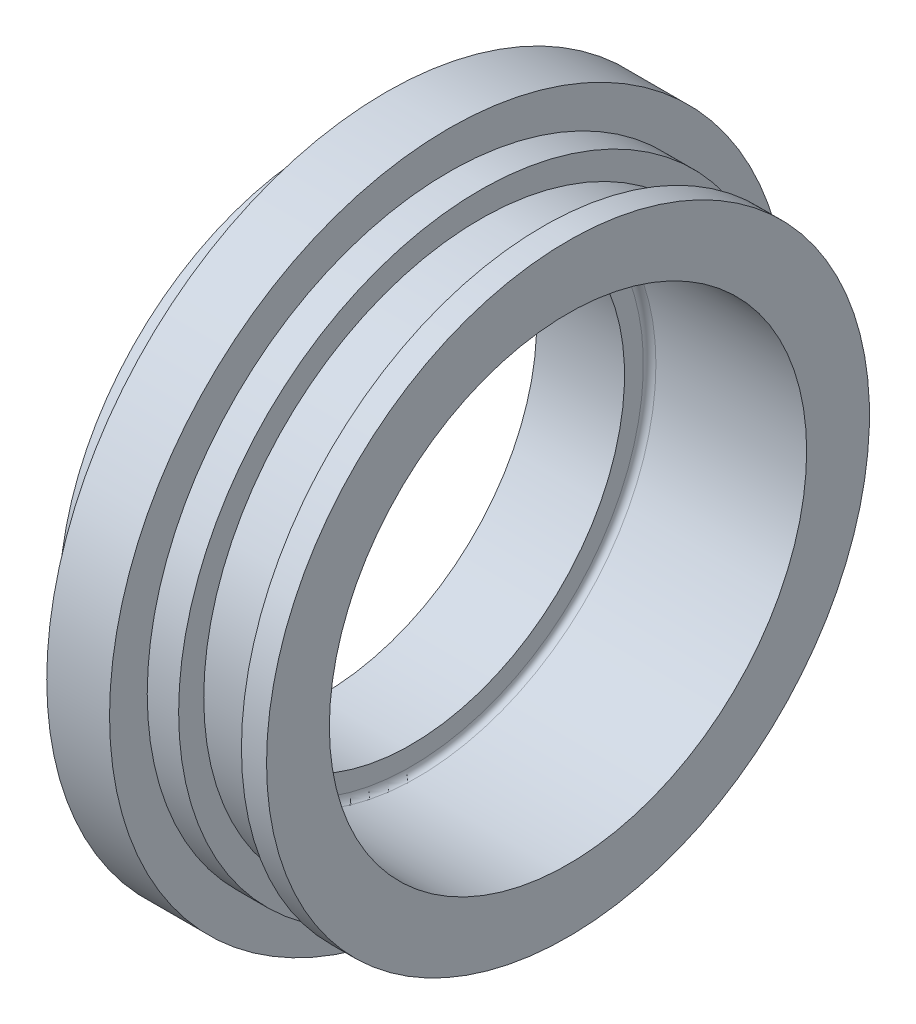
SolidWorks part; units mm, degrees
ref_plane "Přední rovina" through (0, 0, 0) normal (0, 0, 1) x (1, 0, 0)
ref_plane "Horní rovina" through (0, 0, 0) normal (0, 1, 0) x (1, 0, 0)
ref_plane "Pravá rovina" through (0, 0, 0) normal (1, 0, 0) x (0, 0, -1)
sketch "Skica1" plane through (0, 0, 0) normal (0, 0, 1) x (1, 0, 0)
  line L0 (-351.05, 19) -> (-362.55, 19) construction
  line L2 (-346.55, 24) -> (-360.05, 24) construction
  line L3 (-351.05, 19) -> (-362.55, 19) construction
  line L4 (-346.55, 24) -> (-353.05, 24) construction
  line L5 (-379.9367, 0) -> (-341.809, 0) construction
  line L6 (-351.05, 24) -> (-353.05, 24)
  line L7 (-360.55, 24) -> (-360.55, 27)
  line L9 (-360.55, 27) -> (-365.55, 27)
  line L10 (-365.55, 27) -> (-365.55, 20)
  line L11 (-363.55, 19) -> (-351.05, 19)
  line L12 (-351.05, 19) -> (-351.05, 24)
  line L13 (-365.55, -21) -> (-365.55, 21) construction
  line L14 (-353.05, 24) -> (-353.05, 22)
  line L15 (-353.05, 22) -> (-358.05, 22)
  line L16 (-358.05, 22) -> (-358.05, 24)
  line L17 (-358.05, 24) -> (-360.55, 24) construction
  line L18 (-358.05, 24) -> (-360.55, 24)
  line L19 (-365.55, 20) -> (-367.05, 20)
  line L20 (-367.05, 20) -> (-367.55, 21)
  line L21 (-367.55, 21) -> (-370.55, 21)
  line L22 (-370.55, 21) -> (-370.55, 19)
  line L23 (-370.55, 19) -> (-363.55, 19) construction
  line L25 (-363.55, 17.9) -> (-363.55, -17.9) construction
  line L26 (-363.55, 19) -> (-363.55, 17)
  line L27 (-363.55, 17) -> (-370.55, 17)
  line L28 (-370.55, 17) -> (-370.55, 19)
  line L29 (-363.55, 17.9) -> (-363.55, -17.9) construction
  line L30 (-360.55, 27) -> (-360.55, -27) construction
  line L31 (-360.55, 27) -> (-360.55, -27) construction
  point P27 (-364.5565, 19)
  point P30 (0, 0)
  point P31 (0, 0)
  dimension "D1" = 5
  dimension "D2" = 2
  dimension "D3" = 2
  dimension "D4" = 5
  dimension "D5" = 21
  dimension "D6" = 4
  dimension "D7" = 1
  dimension "D8" = 2
  dimension "D9" = 1.5
revolve "Rotovat1" add sketch "Skica1" angle 360 about L5
cosmetic thread "Kosmetický závit1" parameters "D2"=40.773
fillet "Zaoblit1" radius 0.5 1 edges at (-363.55, 0, 19)
